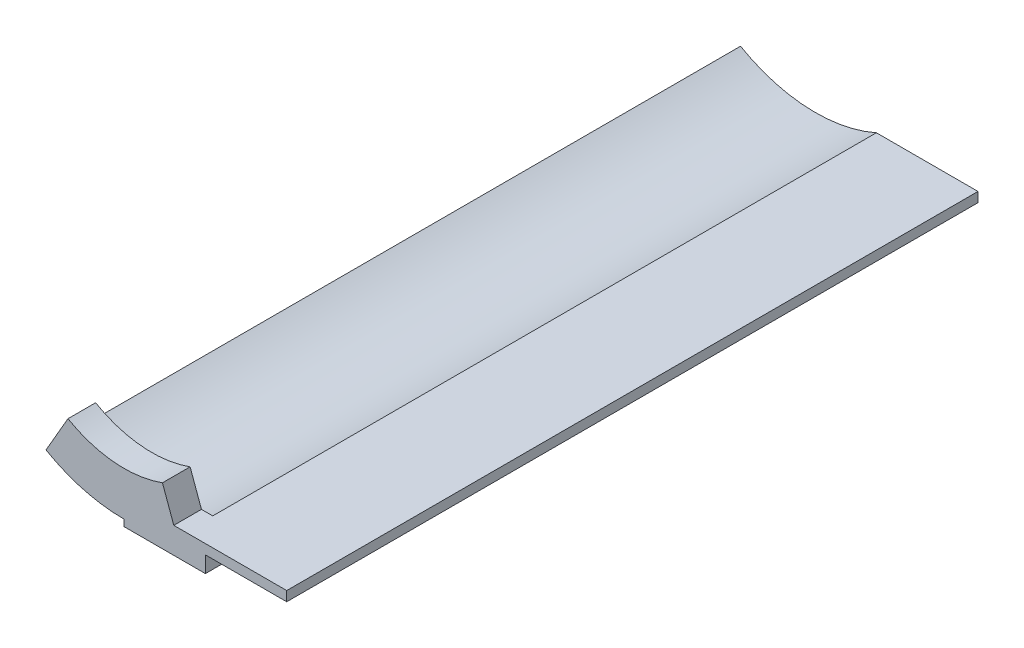
SolidWorks part; units mm, degrees
ref_plane "前视基准面" through (0, 0, 0) normal (0, 0, 1) x (1, 0, 0)
ref_plane "上视基准面" through (0, 0, 0) normal (0, 1, 0) x (1, 0, 0)
ref_plane "右视基准面" through (0, 0, 0) normal (1, 0, 0) x (0, 0, -1)
sketch "草图1" plane through (0, 0, 0) normal (0, 0, 1) x (1, 0, 0)
  line L4 (0, -50) -> (25, -50)
  line L5 (25, -50) -> (25, -45)
  line L6 (25, -45) -> (50, -45)
  line L10 (50, -45) -> (50, -42)
  line L11 (50, -42) -> (15.2867, -42)
  line L12 (11.7997, -32.4194) -> (15.2867, -42)
  line L13 (0, -48) -> (0, -50)
  line L14 (-24, -41.5692) -> (-17.25, -29.8779)
  arc A2 (0, -34.5) -> (-17.25, -29.8779) centre (0, 0) cw
  arc A3 (0, -34.5) -> (11.7997, -32.4194) centre (0, 0) ccw
  arc A5 (0, -48) -> (-24, -41.5692) centre (0, 0) cw
extrude "凸台-拉伸1" add sketch "草图1" along normal blind 8.5
sketch "草图3" plane through (0, 0, 0) normal (0, 0, 1) x (1, 0, 0)
  line L0 (50, -42) -> (23, -42)
  line L1 (50, -42) -> (15.2867, -42) construction
  line L4 (-17.25, -29.8779) -> (-24, -41.5692) construction
  line L5 (-23, -39.8372) -> (-24, -41.5692)
  line L6 (0, -48) -> (0, -50) construction
  line L7 (0, -48) -> (0, -50)
  line L8 (0, -50) -> (25, -50) construction
  line L9 (0, -50) -> (25, -50)
  line L10 (25, -50) -> (25, -45)
  line L11 (25, -45) -> (50, -45)
  line L12 (50, -45) -> (50, -42)
  line L13 (23, -42) -> (18.7617, -42)
  arc A0 (0, -46) -> (-23, -39.8372) centre (0, 0) cw
  arc A1 (-24, -41.5692) -> (0, -48) centre (0, 0) ccw
  arc A2 (0, -46) -> (18.7617, -42) centre (0, 0) ccw
extrude "凸台-拉伸5" add sketch "草图3" against normal blind 204
